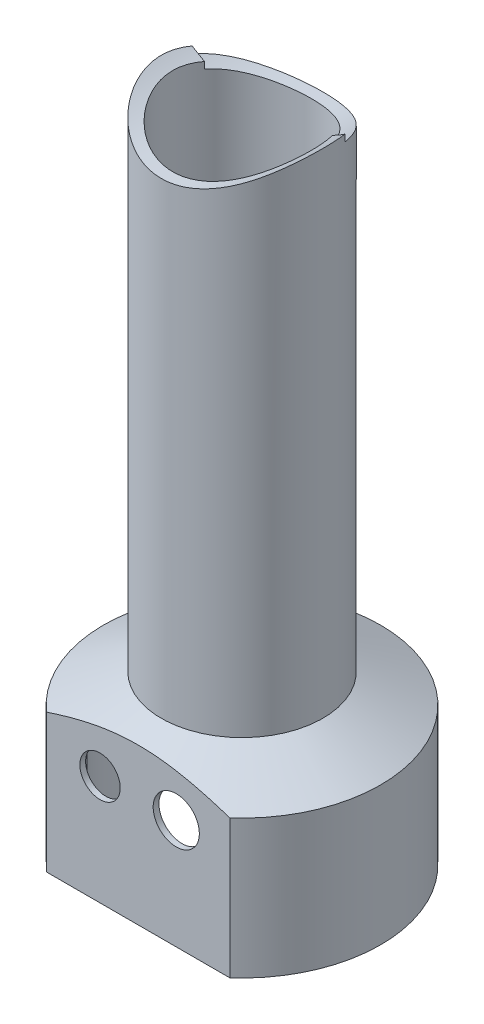
SolidWorks part; units mm, degrees
ref_plane "Front Plane" through (0, 0, 0) normal (0, 0, 1) x (1, 0, 0)
ref_plane "Top Plane" through (0, 0, 0) normal (0, 1, 0) x (1, 0, 0)
ref_plane "Right Plane" through (0, 0, 0) normal (1, 0, 0) x (0, 0, -1)
sketch "Sketch1" plane through (0, 0, 0) normal (0, 1, 0) x (1, 0, 0)
  circle A0 centre (0, 0) radius 14
  dimension "D1" = 28
extrude "Boss-Extrude1" add sketch "Sketch1" along normal blind 105
ref_plane "Plane1" through (0, 0, -14) normal (0, 0, -1) x (-1, 0, 0)
sketch "Sketch2" plane through (0, 0, -14) normal (0, 0, -1) x (-1, 0, 0)
  line L0 (14, 105) -> (-14, 105) construction
  line L1 (14, 105) -> (-14, 105)
  circle A0 centre (0, 105) radius 24
  dimension "D1" = 48
extrude "Cut-Extrude1" cut sketch "Sketch2" against normal through all contours A0
sketch "Sketch4" plane through (0, 0, -14) normal (0, 0, -1) x (-1, 0, 0)
  line L1 (-14, 0) -> (14, 0) construction
  line L2 (-14, 85.5064) -> (-14, 0) construction
  line L3 (-14, 85.5064) -> (-14, 0) construction
  circle A0 centre (0, 105) radius 25
  dimension "D1" = 50
  dimension "D2" = 105
  dimension "D3" = 14
extrude "Cut-Extrude2" cut sketch "Sketch4" against normal blind 9.4 contours A0 region at (0, 105, -14)
sketch "Sketch5" plane through (0, 0, 0) normal (0, -1, 0) x (1, 0, 0)
  circle A0 centre (0, 0) radius 12
  dimension "D1" = 24
extrude "Cut-Extrude3" cut sketch "Sketch5" against normal blind 123
ref_plane "Plane2" through (0, 0, 14) normal (0, 0, 1) x (1, 0, 0)
ref_plane "Plane3" through (0, -5, 0) normal (0, -1, 0) x (-1, 0, 0)
sketch "Sketch8" plane through (0, -5, 0) normal (0, -1, 0) x (-1, 0, 0)
  circle A0 centre (0, 0) radius 24
  circle A1 centre (0, 0) radius 22
  dimension "D1" = 48
  dimension "D2" = 44
sketch "Sketch10" plane through (0, 0, 0) normal (0, -1, 0) x (-1, 0, 0)
  circle A0 centre (0, 0) radius 14 construction
  circle A1 centre (0, 0) radius 14
  circle A3 centre (0, 0) radius 12
  dimension "D1" = 24
loft "Loft6" add section "Sketch10" section "Sketch8" connector at (12.9174, 0, -5.3982) connector at (22.9916, -5, -6.8838)
loft "Cut-Loft1" cut section "Sketch10<4>" section "Sketch8<6>" connector at (-6.9186, 0, -9.8048) connector at (3.6598, -5, -21.6934)
sketch "Sketch10<4>" plane through (0, 0, 0) normal (0, -1, 0) x (-1, 0, 0) same geometry as "Sketch10"
sketch "Sketch8<6>" plane through (0, -5, 0) normal (0, -1, 0) x (-1, 0, 0) same geometry as "Sketch8"
sketch "Sketch12" plane through (0, -5, 0) normal (0, -1, 0) x (1, 0, 0)
  circle A0 centre (0, 0) radius 24 construction
  circle A2 centre (0, 0) radius 24
  circle A4 centre (0, 0) radius 19
  dimension "D1" = 38
extrude "Boss-Extrude2" add sketch "Sketch12" along normal blind 24
sketch "Sketch13" plane through (0, -29, 0) normal (0, -1, 0) x (1, 0, 0)
  line L0 (-15.2028, 15.2028) -> (15.2028, 15.2028) construction
  line L1 (15.2028, 15.2028) -> (15.2028, -15.2028) construction
  line L2 (15.2028, -15.2028) -> (-15.2028, -15.2028) construction
  line L3 (-15.2028, -15.2028) -> (-15.2028, 15.2028) construction
  circle A0 centre (-15.2028, 15.2028) radius 1.6
  circle A1 centre (15.2028, 15.2028) radius 1.6
  circle A2 centre (15.2028, -15.2028) radius 1.6
  circle A3 centre (-15.2028, -15.2028) radius 1.6
  circle A7 centre (0, 0) radius 24 construction
  dimension "D1" = 3.2
  dimension "D2" = 3.2
  dimension "D3" = 3.2
  dimension "D4" = 3.2
  dimension "D6" = 2.5
  dimension "D5" = 2.5
  dimension "D7" = 2.5
extrude "Cut-Extrude4" cut sketch "Sketch13" against normal blind 8
ref_plane "Plane4" through (0, 0, 24) normal (0, 0, 1) x (1, 0, 0)
sketch "Sketch15" plane through (0, 0, 24) normal (0, 0, 1) x (1, 0, 0)
  line L0 (-24, -5) -> (-24, -29) construction
  line L1 (-24, -29) -> (24, -29) construction
  line L2 (24, -29) -> (24, -5) construction
  line L4 (-24, -5) -> (-24, -29)
  line L5 (-24, -29) -> (24, -29)
  line L6 (24, -29) -> (24, -5)
  line L8 (24, -5) -> (14, 0) construction
  line L9 (14, 0) -> (-14, 0) construction
  line L10 (-14, 0) -> (-24, -5) construction
  line L11 (24, -5) -> (14, 0)
  line L12 (14, 0) -> (-14, 0)
  line L13 (-14, 0) -> (-24, -5)
extrude "Cut-Extrude6" cut sketch "Sketch15" against normal blind 6
sketch "Sketch17" plane through (0, 0, 18) normal (0, 0, 1) x (1, 0, 0)
  line L0 (15.8745, -29) -> (15.8745, -5) construction
  line L1 (-15.8745, -5) -> (-15.8745, -29) construction
  line L2 (15.8745, -29) -> (15.8745, -5)
  line L3 (-15.8745, -5) -> (-15.8745, -29)
  line L4 (-15.8745, -29) -> (15.8745, -29)
  spline S0 degree 3 poles (-832.1082, 1815.2928) (-124.6922, -173.6737) (-88.3609, -25.0052) (-10.7088, -3.4584) (-9.398, -3.1348) (-7.4072, -2.7275) (-6.7395, -2.6049) (-5.3945, -2.3901) (-4.7155, -2.2978) (-2.6848, -2.0756) (-1.335, -1.9996) (1.3561, -2.0004) (2.6975, -2.0771) (5.3727, -2.3697) (6.7064, -2.5851) (8.7025, -2.992) (9.3683, -3.1419) (10.6901, -3.4636) (11.3464, -3.6354) (87.231, -24.6808) (112.9234, -166.2943) (979.6225, 1741.9831) knots -7.220929 -7.220929 -7.220929 -7.220929 0.125 0.125 0.25 0.25 0.3125 0.3125 0.375 0.375 0.5 0.5 0.625 0.625 0.75 0.75 0.8125 0.8125 0.875 0.875 8.080062 8.080062 8.080062 8.080062 only from (-15.8745, -5) to (15.8745, -5) construction
  spline S1 degree 3 poles (-15.8745, -5) (-14.5949, -4.5768) (-12.0196, -3.782) (-9.398, -3.1348) (-7.4072, -2.7275) (-6.7395, -2.6049) (-5.3945, -2.3901) (-4.7155, -2.2978) (-2.6848, -2.0756) (-1.335, -1.9996) (1.3561, -2.0004) (2.6975, -2.0771) (5.3727, -2.3697) (6.7064, -2.5851) (8.7025, -2.992) (9.3683, -3.1419) (10.6901, -3.4636) (11.3464, -3.6354) (13.3042, -4.1784) (14.5945, -4.5767) (15.8745, -5) knots 0 0 0 0 0.125 0.25 0.25 0.3125 0.3125 0.375 0.375 0.5 0.5 0.625 0.625 0.75 0.75 0.8125 0.8125 0.875 0.875 1 1 1 1
extrude "Boss-Extrude7" add sketch "Sketch17" against normal blind 1
sketch "Sketch19" plane through (0, 0, 17) normal (0, 0, -1) x (-1, 0, 0)
  line L0 (8.4853, -29) -> (-8.4853, -29) construction
  line L1 (8.4853, -29) -> (-8.4853, -29)
  line L2 (8.4853, -29) -> (12.6028, -29)
  line L3 (12.6028, -29) -> (12.6028, -4.6864)
  line L4 (-8.4853, -29) -> (-12.6028, -29)
  line L5 (-12.6028, -29) -> (-12.6028, -4.6864)
  spline S0 degree 3 poles (575.4679, 1910.1756) (130.4121, -150.5856) (79.891, -14.9514) (5.8809, -3.4286) (4.7108, -3.2803) (2.3615, -3.077) (1.1849, -3.0229) (-1.1727, -3.0225) (-2.3523, -3.0765) (-4.6997, -3.2791) (-5.8709, -3.4272) (-79.8009, -14.9277) (-128.7209, -150.0521) (-599.1176, 1903.1261) knots -7.582552 -7.582552 -7.582552 -7.582552 0.25 0.25 0.375 0.375 0.5 0.5 0.625 0.625 0.75 0.75 8.560332 8.560332 8.560332 8.560332 only from (13.9642, -5) to (-13.9642, -5) construction
  spline S1 degree 3 poles (13.9642, -5) (11.671, -4.4602) (9.3686, -3.9716) (5.8809, -3.4286) (4.7108, -3.2803) (2.3615, -3.077) (1.1849, -3.0229) (-1.1727, -3.0225) (-2.3523, -3.0765) (-4.6997, -3.2791) (-5.8709, -3.4272) (-9.3647, -3.9706) (-11.6694, -4.4598) (-13.9642, -5) knots 0 0 0 0 0.25 0.25 0.375 0.375 0.5 0.5 0.625 0.625 0.75 0.75 1 1 1 1
  line M2 (-8.4853, -5) -> (-8.4853, -29)
  line M3 (-8.4853, -29) -> (8.4853, -29)
  line M4 (8.4853, -29) -> (8.4853, -5)
  line M5 (8.4853, -5) -> (13.9642, -5)
  line M7 (-13.9642, -5) -> (-8.4853, -5)
  dimension "D1" = 1
  dimension "D2" = 1
extrude "Cut-Extrude7" cut sketch "Sketch19" along normal blind 10 contours L5 L3 M7 M2 M3 M4 M5 | L2 L3 M5 M4 | L5 L4 M2 M7 region at (-10.544, -17, 17) region at (0, -15.9924, 17) region at (10.544, -17, 17)
sketch "Sketch20" plane through (0, 0, 18) normal (0, 0, 1) x (1, 0, 0)
  line L0 (-15.8745, -10) -> (-6.6028, -10) construction
  line L1 (-15.8745, -5) -> (-15.8745, -29) construction
  line L2 (-6.6028, -10) -> (6.6028, -10) construction
  line L3 (6.6028, -10) -> (15.8745, -10) construction
  line L4 (15.8745, -29) -> (15.8745, -5) construction
  circle A0 centre (6.6028, -10) radius 4
  circle A1 centre (-6.6028, -10) radius 3.5
  dimension "D1" = 8
  dimension "D2" = 7
  dimension "D3" = 6
  dimension "D4" = 6
  dimension "D5" = 5
extrude "Cut-Extrude8" cut sketch "Sketch20" against normal blind 10
sketch "Sketch22" plane through (0, -29, 0) normal (0, -1, 0) x (1, 0, 0)
  line L0 (-15.8745, 18) -> (15.8745, 18) construction
  line L1 (-15.8745, 18) -> (15.8745, 18)
  arc A0 (-15.8745, 18) -> (15.8745, 18) centre (0, 0) ccw construction
  arc A1 (-15.8745, 18) -> (15.8745, 18) centre (0, 0) ccw
  circle A2 centre (-15.2028, 15.2028) radius 1.05
  circle A3 centre (15.2028, 15.2028) radius 1.05
  circle A4 centre (15.2028, -15.2028) radius 1.05
  circle A5 centre (-15.2028, -15.2028) radius 1.05
  dimension "D1" = 2.1
  dimension "D2" = 2.1
  dimension "D3" = 2.1
  dimension "D4" = 2.1
extrude "Boss-Extrude8" add sketch "Sketch22" along normal blind 1 separate body
other "Save Bodies1" [suppressed]
delete or keep bodies "Body-Delete/Keep 2" type delete bodies bodies 117
ref_plane "Plane5" through (0, 0, -12) normal (0, 0, 1) x (1, 0, 0)
sketch "Sketch23" plane through (0, 0, -12) normal (0, 0, 1) x (1, 0, 0)
  line L0 (14, 0) -> (-14, 0) construction
  line L1 (14, 0) -> (14, 85.5064) construction
  line L2 (-14, 85.5064) -> (-14, 0) construction
  line L3 (14, 0) -> (14, 85.5064) construction
  line L4 (-14, 85.5064) -> (-14, 0) construction
  line L5 (-14, 4) -> (14, 4) construction
  circle A0 centre (0, 4) radius 2
  dimension "D1" = 4
  dimension "D2" = 4
extrude "Cut-Extrude9" cut sketch "Sketch23" against normal blind 5 and the other way blind 10
other "Save Bodies2" [suppressed]
